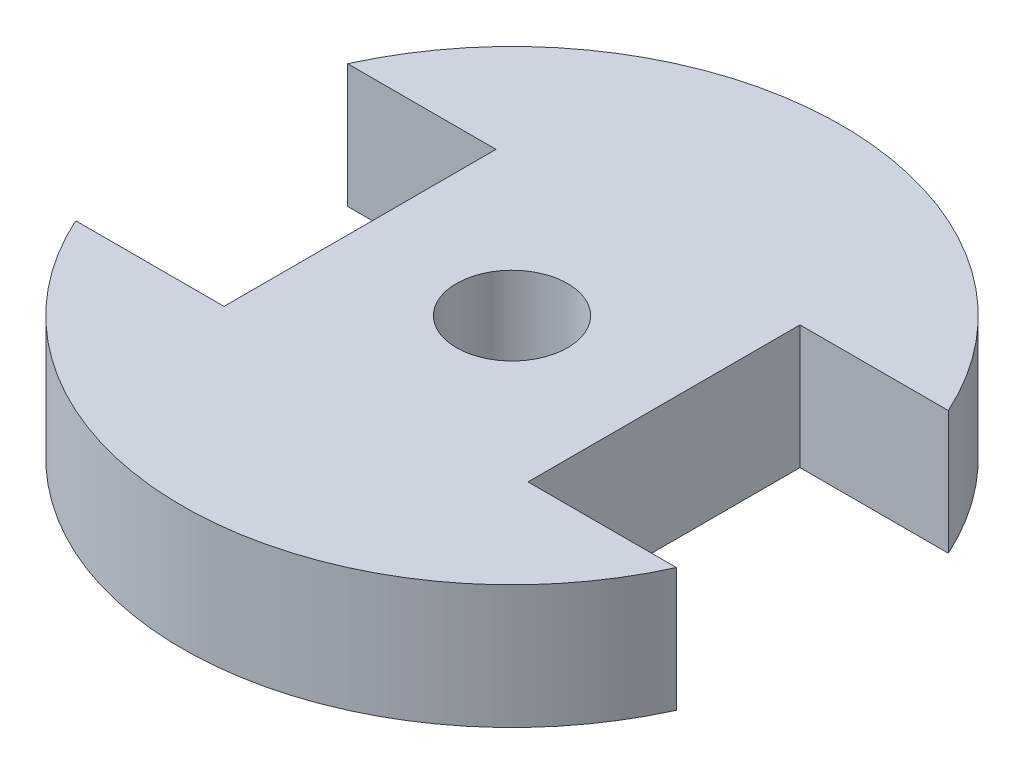
SolidWorks part; units mm, degrees
ref_plane "Front Plane" through (0, 0, 0) normal (0, 0, 1) x (1, 0, 0)
ref_plane "Top Plane" through (0, 0, 0) normal (0, 1, 0) x (1, 0, 0)
ref_plane "Right Plane" through (0, 0, 0) normal (1, 0, 0) x (0, 0, -1)
sketch "Sketch1" plane through (0, 0, 0) normal (0, 1, 0) x (1, 0, 0)
  line L0 (-12.1479, 5.5) -> (-6.1479, 5.5)
  line L1 (-6.1479, 5.5) -> (-6.1479, -5.5)
  line L2 (-6.1479, -5.5) -> (-12.1479, -5.5)
  line L3 (0, 0) -> (-6.1479, 0) construction
  line L4 (12.1479, 5.5) -> (6.1479, 5.5)
  line L5 (6.1479, 5.5) -> (6.1479, -5.5)
  line L6 (6.1479, -5.5) -> (12.1479, -5.5)
  line L8 (6.1479, 0) -> (0, 0) construction
  circle A0 centre (0, 0) radius 15.875 construction
  arc A1 (-12.1479, -5.5) -> (12.1479, -5.5) centre (0, 0) ccw
  circle A2 centre (0, 0) radius 2.25
  arc A3 (12.1479, 5.5) -> (-12.1479, 5.5) centre (0, 0) ccw
  arc A4 (-12.1479, 5.5) -> (-12.1479, -5.5) centre (0, 0) ccw construction
  arc A5 (12.1479, -5.5) -> (12.1479, 5.5) centre (0, 0) ccw construction
  point P16 (12.1479, 5.3562)
  dimension "D1" = 31.75
  dimension "D2" = 2.54
  dimension "D4" = 4.5
  dimension "D3" = 6
  dimension "D5" = 11
extrude "Boss-Extrude1" add sketch "Sketch1" along normal blind 5
